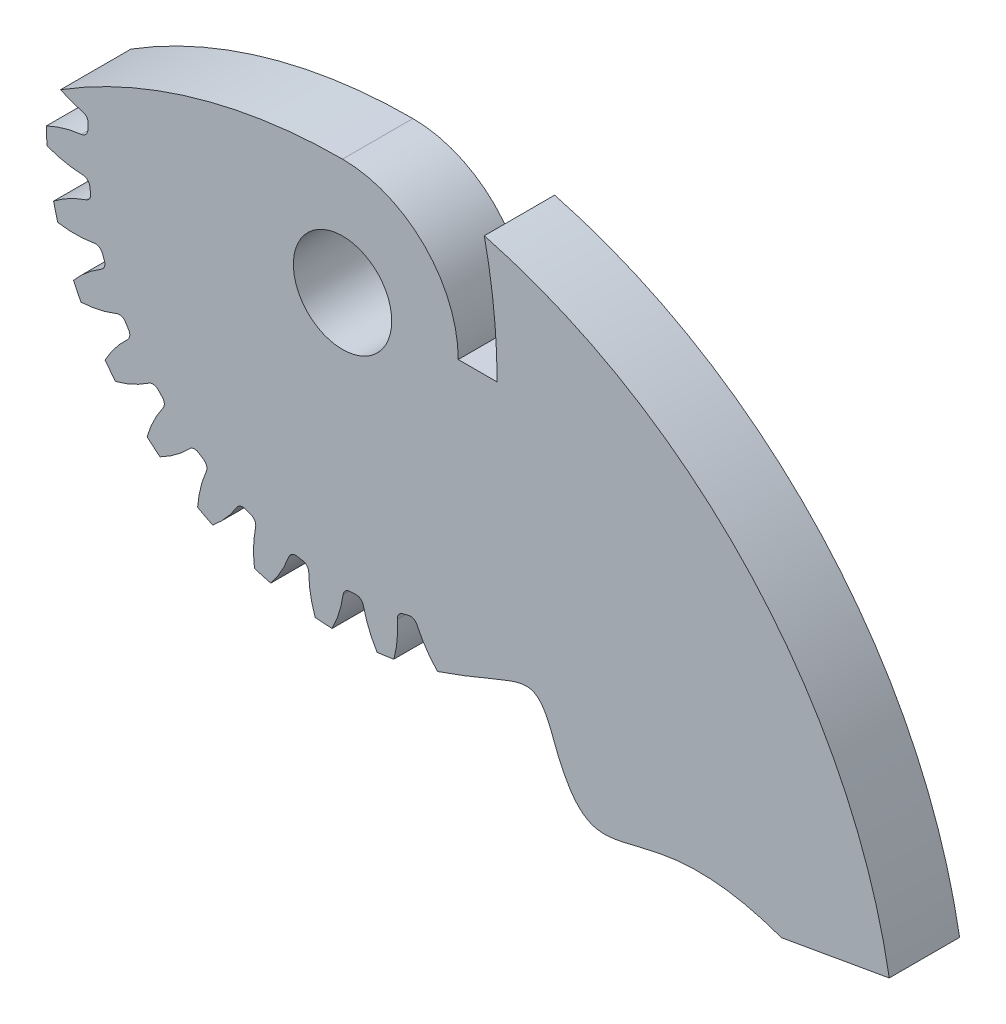
SolidWorks part; units mm, degrees
material "ABS"
ref_plane "Front" through (0, 0, 0) normal (0, 0, 1) x (1, 0, 0)
ref_plane "Top" through (0, 0, 0) normal (0, 1, 0) x (1, 0, 0)
ref_plane "Right" through (0, 0, 0) normal (1, 0, 0) x (0, 0, -1)
sketch "Sketch3" plane through (0, 0, 0) normal (0, 0, 1) x (1, 0, 0)
  circle A0 centre (0, 0) radius 40.64
  dimension "od" = 81.28
extrude "gearBody" add sketch "Sketch3" along normal blind 9.652
sketch "Sketch2" plane through (0, 0, 0) normal (0, 0, 1) x (1, 0, 0)
  line L0 (0, 0) -> (34.0786, 14.1158) construction
  line L1 (45.4751, -11.4855) -> (0, 0) construction
  line L2 (0, 0) -> (36.3143, 0) construction
  line L3 (38.0972, -0.458) -> (37.8451, -4.4001) construction
  line L5 (37.9712, -2.4291) -> (0, 0) construction
  line L7 (0, 0) -> (36.8864, 0) construction
  arc A0 (36.879, -0.7403) -> (36.6727, -3.9649) centre (0, 0) ccw construction
  arc A1 (40.637, 0.4947) -> (40.2427, -5.6687) centre (0, 0) ccw construction
  arc A2 (38.0972, -0.458) -> (37.8451, -4.4001) centre (0, 0) ccw construction
  arc A3 (34.9015, -2.6404) -> (34.9534, -1.8283) centre (0, 0) ccw
  arc A4 (45.4751, -11.4855) -> (35.6466, -3.6712) centre (32.0022, -18.3431) ccw
  arc A5 (45.4751, -11.4855) -> (46.5679, 5.5974) centre (0, 0) ccw
  arc A6 (46.5679, 5.5974) -> (35.8238, -0.9008) centre (34.0786, 14.1158) cw
  arc A7 (34.9534, -1.8283) -> (35.8238, -0.9008) centre (35.9376, -1.8798) cw
  arc A8 (35.6466, -3.6712) -> (34.9015, -2.6404) centre (35.8842, -2.7147) cw
  point P6 (46.5679, 5.5974)
  point P22 (45.4751, -11.4855)
  dimension "baseDia" = 73.7729
  dimension "od" = 81.28
  dimension "pd" = 76.2
  dimension "rd" = 70.0024
  dimension "rFillet" = 0.9855
  dimension "pointX" = 46.5679
  dimension "pointY" = 5.5974
  dimension "CTT" = 3.9421
  dimension "flankCenterAngle" = 22.5
extrude "toothCut" cut sketch "Sketch2" along normal through all
pattern_circular "CirPattern1" count 30 over 360 about axis through (0, 0, 9.652) along (0, 0, -1) of "toothCut"
sketch "hub1Dia" plane through (0, 0, 0) normal (0, 0, -1) x (-1, 0, 0)
  circle A0 centre (0, 0) radius 12.7
  dimension "hub1Dia" = 25.4
sketch "hub2Dia" plane through (0, 0, 9.652) normal (0, 0, 1) x (1, 0, 0)
  circle A0 centre (0, 0) radius 12.7
  dimension "hub2dia" = 25.4
sketch "boreDia" plane through (0, 0, 0) normal (0, 0, 1) x (1, 0, 0)
  circle A0 centre (0, 0) radius 6.7469
  dimension "boreDia" = 13.4937
extrude "bore" cut sketch "boreDia" against normal mid plane 25400
sketch "Sketch4" plane through (0, 0, 9.652) normal (0, 0, 1) x (1, 0, 0)
  circle A0 centre (0, -57.15) radius 76.1746
  arc A2 (-41.7195, 6.5842) -> (41.7195, 6.5842) centre (0, 0) cw
  dimension "D1" = 152.3492
  dimension "D2" = 57.15
extrude "Cut-Extrude1" cut sketch "Sketch4" against normal through all contours A0 region at (0, 26.0638, 9.652)
sketch "Sketch5" plane through (0, 0, 9.652) normal (0, 0, 1) x (1, 0, 0)
  line L0 (0, 19.0246) -> (21.5163, 3.7176)
  line L1 (21.5163, 3.7176) -> (8.9608, -26.928)
  line L2 (8.9608, -26.928) -> (13.028, -38.4952)
  line L3 (0, 0) -> (0, -57.15) construction
  line L4 (0, -57.15) -> (-54.1615, -3.586) construction
  line L5 (0, -57.15) -> (65.9691, -95.2373) construction
  line L9 (0, -57.15) -> (75.0173, -43.9224) construction
  line L12 (60.232, -46.5295) -> (75.0173, -43.9224)
  line L13 (0, -57.15) -> (29.696, -40.005) construction
  line L14 (29.696, -40.005) -> (26.521, -34.5057) construction
  circle A1 centre (0, -57.15) radius 76.1746 construction
  arc A5 (0, 19.0246) -> (75.0173, -43.9224) centre (0, -57.15) cw
  circle A6 centre (0, -57.15) radius 21.59 construction
  circle A12 centre (49.4934, -85.725) radius 40.64 construction
  spline S0 degree 3 poles (13.028, -38.4952) (20.557, -35.948) (26.6517, -31.726) (34.6651, -56.7545) (39.5345, -39.0169) (60.232, -46.5295) knots 0 0 0 0 0.118515 0.218515 1 1 1 1
  point P28 (21.569, -56.1981)
  dimension "D1" = 43.18
  dimension "D3" = 81.28
  dimension "D6" = 152.3492
  dimension "D2" = 120
  dimension "D4" = 57.15
  dimension "D8" = 57.15
  dimension "D7" = 60
  dimension "D9" = 34.29
  dimension "D10" = 6.35
  dimension "D5" = 80
extrude "Boss-Extrude1" add sketch "Sketch5" against normal up to surface (9.652 mm away) up to face at (6.7469, 0, 0)
sketch "Sketch6" plane through (0, 0, 9.652) normal (0, 0, 1) x (1, 0, 0)
  line L1 (-41.2993, 3.0747) -> (-42.3397, 6.1739)
  line L2 (15.875, 0) -> (21.209, 0)
  circle A0 centre (0, -57.15) radius 76.1746 construction
  arc A1 (75.0173, -43.9224) -> (-34.0662, 10.9827) centre (0, -57.15) ccw construction
  circle A2 centre (0, 0) radius 15.875 construction
  arc A3 (0, 15.875) -> (15.875, 0) centre (0, 0) cw
  arc A4 (19.4523, 16.499) -> (-42.3397, 6.1739) centre (0, -57.15) ccw
  arc A5 (0, 15.875) -> (-41.2993, 3.0747) centre (0, -57.15) ccw
  circle A6 centre (0, 0) radius 21.209 construction
  circle A8 centre (-57.15, 0) radius 78.359 construction
  arc A9 (21.209, 0) -> (19.4523, 16.499) centre (-57.15, 0) ccw
  dimension "D4" = 57.15
  dimension "D1" = 31.75
  dimension "D2" = 42.418
  dimension "D3" = 156.718
extrude "Cut-Extrude2" cut sketch "Sketch6" against normal through all
equation "\"Bodytube_OD\" = 6.17in"
equation "\"Bodytube_ID\" = 5.998in"
equation "\"Fwd_Tube_Length\" = 40in"
equation "\"Mid_Tube_Length\" = 1in"
equation "\"Aft_Section_Length\"= 39in"
equation "\"Mid_Coupler_Length\"= 13in"
equation "\"Aft_Lower_Length\"= 22in"
equation "\"AB_Coupler_OD_Length\"= 1in"
equation "\"AB_Coupling_Section_Length\"= 0.375in"
equation "\"AB_Coupler_Length\"= \"AB_Coupler_OD_Length\" + \"AB_Coupling_Section_Length\" * 2"
equation "\"Cutout_Angle\" = 80"
equation "\"AB_Paddle_Height\" = 0.375in"
equation "\"AB_Coupler_Num_Screws\"= 4"
equation "\"Num_Cutouts\" = 3"
equation "\"AB_Coupler_OD\"= 6.17in"
equation "\"AB_Coupler_ID\"= 5.75in"
equation "\"AB_Coupler_Surface_Diameter\"= 5.998in"
equation "\"AB_Coupling_Screw_Diameter\"= 0.1065in"
equation "\"AB_Central_Bushing_Length\" = .4724in"
equation "\"Lead_Screw_Dist\" = 3.4in"
equation "\"Lead_Screw_Diam\" = 0.386in"
equation "\"Lead_Screw_Length\" = (\"Mid_Coupler_Length\" + 2*0.375in + 2*0.5in)"
equation "\"Paddle_Pin_Offset\" = .25in"
equation "\"Paddle_Pin_Radius\" = 2.25in"
equation "\"Fwd_BKHD_From_Top\" = 18in"
equation "\"D1@Sketch4\"=\"Bodytube_ID\""
equation "\"D2@Sketch4\"=\"Paddle_Pin_Radius\""
equation "\"D3@Sketch5\"=\"Paddle_Gear_OD\""
equation "\"D4@Sketch5\"=\"Paddle_Pin_Radius\""
equation "\"Motor_OD\" = 4in"
equation "\"Aft_Upper_Length\"= \"Aft_Section_Length\" - \"Aft_Lower_Length\" - \"AB_Coupler_OD_Length\""
equation "\"Paddle_Gear_OD\" = 3.2in"
equation "\"D5@Sketch5\"=\"Cutout_Angle\""
equation "\"D6@Sketch5\"=\"Bodytube_ID\""
equation "\"D1@Sketch6\"=\"AB_Coupler_ID\"-2*\"Paddle_Pin_Radius\""
equation "\"D2@Sketch6\"=\"Bodytube_OD\"-2*\"Paddle_Pin_Radius\""
equation "\"D3@Sketch6\"=\"Bodytube_OD\""
equation "\"D4@Sketch6\"=\"Paddle_Pin_Radius\""
equation "\"D8@Sketch5\"=\"Paddle_Pin_Radius\""
equation "\"Drive_Gear_OD\" = 1.7in"
equation "\"Fin_Thickness\"= .118in"
equation "\"Guiderail_Cutout_Diameter\"= 1.5in"
equation "\"DB9_Hole_Dist\" = 25mm"
equation "\"D1@Sketch5\"=\"Drive_Gear_OD\""
